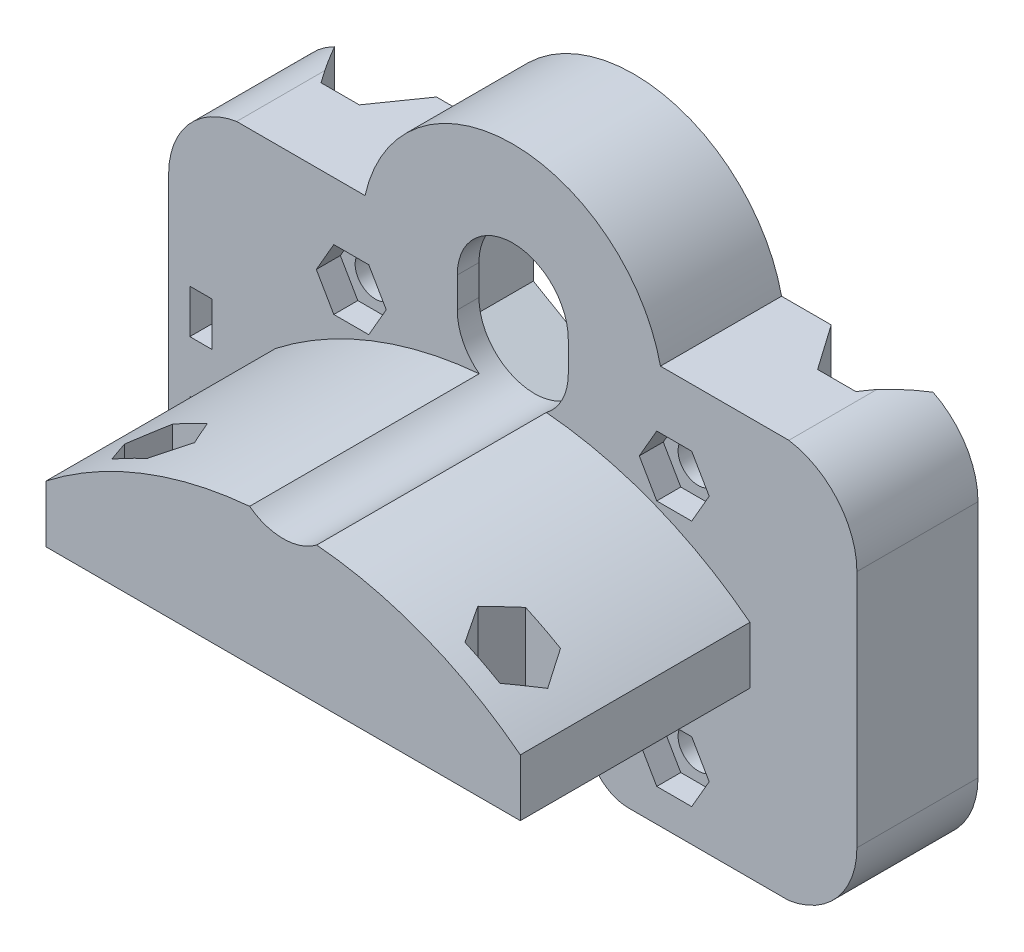
SolidWorks part; units mm, degrees
ref_plane "Front Plane" through (0, 0, 0) normal (0, 0, 1) x (1, 0, 0)
ref_plane "Top Plane" through (0, 0, 0) normal (0, 1, 0) x (1, 0, 0)
ref_plane "Right Plane" through (0, 0, 0) normal (1, 0, 0) x (0, 0, -1)
sketch "Sketch1" plane through (0, 0, 0) normal (0, 0, 1) x (1, 0, 0)
  line L0 (34.1, -14.8502) -> (34.1, 8.8502)
  line L1 (-34.1, -14.8502) -> (-34.1, 8.8502)
  line L2 (-14.6356, 16.75) -> (-27.3591, 16.75)
  line L3 (14.6356, 16.75) -> (27.3591, 16.75)
  line L4 (-11.5, -22.75) -> (-27.5591, -22.75)
  line L5 (11.5, -22.75) -> (27.3591, -22.75)
  line L6 (7.5, -18.75) -> (7.5, -16.0002)
  line L7 (-7.5, -16.0002) -> (-7.5, -18.75)
  line L8 (0, -8.5446) -> (0, 28.5) construction
  line L9 (34.1, 0) -> (-34.1, 0) construction
  arc A0 (27.3591, -22.75) -> (34.1, -14.8502) centre (26.1005, -14.8502) ccw
  arc A1 (7.5, -18.75) -> (11.5, -22.75) centre (11.5, -18.75) ccw
  arc A2 (34.1, 8.8502) -> (27.3591, 16.75) centre (26.1005, 8.8502) ccw
  arc A3 (-34.1, 8.8502) -> (-27.3591, 16.75) centre (-26.1005, 8.8502) cw
  arc A4 (-27.3591, -22.75) -> (-34.1, -14.8502) centre (-26.1005, -14.8502) cw
  arc A5 (-7.5, -18.75) -> (-11.5, -22.75) centre (-11.5, -18.75) cw
  arc A6 (14.6356, 16.75) -> (-14.6356, 16.75) centre (0, 13.5101) ccw
  arc A7 (7.5, -16.0892) -> (-7.5, -16.0892) centre (0, -16.0447) ccw
  circle A8 centre (16.0001, 8) radius 2
  circle A9 centre (16.0001, -16.5) radius 2
  circle A10 centre (-16.0001, -16.5) radius 2
  circle A11 centre (-16.0001, 8) radius 2
  dimension "D1" = 4
  dimension "D2" = 4.0001
  dimension "D3" = 7.9995
  dimension "D4" = 4.0001
  dimension "D5" = 7.5
  dimension "D6" = 14.9899
  dimension "D7" = 7.5001
  dimension "D8" = 14.6356
  dimension "D9" = 16.0001
  dimension "D10" = 26.1005
  dimension "D11" = 27.3591
  dimension "D12" = 8
  dimension "D13" = 8.8502
  dimension "D14" = 14.8502
  dimension "D15" = 16.0002
  dimension "D18" = 27.5591
  dimension "D25" = 16.5
extrude "Boss-Extrude1" add sketch "Sketch1" along normal blind 7.5 and the other way blind 4.5 contours A7 L6 A1 L5 A0 L0 A2 L3 A6 L2 A3 L1 A4 L4 A5 L7 A10 A9 A8 A11 region at (0, 0.408, 0)
sketch "Sketch3" plane through (0, 0, 7.5) normal (0, 0, 1) x (1, 0, 0)
  line L0 (0, 28.5) -> (0, -8.5446) construction
  line L1 (-19.4642, 8) -> (-17.7321, 5)
  line L2 (-17.7321, 5) -> (-14.268, 5)
  line L3 (-14.268, 5) -> (-12.536, 8)
  line L4 (-12.536, 8) -> (-14.268, 11)
  line L5 (-14.268, 11) -> (-17.7321, 11)
  line L6 (-5.5, 11.5) -> (-5.5, 14.5)
  line L7 (5.5, 11.5) -> (5.5, 14.5)
  line L8 (12.536, 8) -> (14.268, 11)
  line L9 (14.268, 5) -> (12.536, 8)
  line L10 (17.7321, 5) -> (14.268, 5)
  line L11 (19.4642, 8) -> (17.7321, 5)
  line L12 (17.7321, 11) -> (19.4642, 8)
  line L13 (14.268, 11) -> (17.7321, 11)
  line L14 (-34.1, -4.25) -> (34.1, -4.25) construction
  line L15 (-34.1, -14.8502) -> (-34.1, 8.8502) construction
  line L16 (-17.7321, -19.5) -> (-19.4642, -16.5)
  line L17 (-19.4642, -16.5) -> (-17.7321, -13.5)
  line L18 (-17.7321, -13.5) -> (-14.268, -13.5)
  line L19 (-14.268, -13.5) -> (-12.536, -16.5)
  line L20 (-12.536, -16.5) -> (-14.268, -19.5)
  line L21 (-14.268, -19.5) -> (-17.7321, -19.5)
  line L22 (17.7321, -19.5) -> (19.4642, -16.5)
  line L23 (19.4642, -16.5) -> (17.7321, -13.5)
  line L24 (17.7321, -13.5) -> (14.268, -13.5)
  line L25 (14.268, -13.5) -> (12.536, -16.5)
  line L26 (34.1, -14.8502) -> (34.1, 8.8502) construction
  line L27 (11.5, -22.75) -> (27.3591, -22.75) construction
  line L28 (-17.7321, 11) -> (-19.4642, 8)
  line L29 (12.536, -16.5) -> (14.268, -19.5)
  line L30 (14.268, -19.5) -> (17.7321, -19.5)
  arc A0 (14.6356, 16.75) -> (-14.6356, 16.75) centre (0, 13.5101) ccw construction
  circle A1 centre (-16.0001, 8) radius 3 construction
  arc A2 (7.5, -16.0892) -> (-7.5, -16.0892) centre (0, -16.0447) ccw construction
  arc A3 (-5.5, 14.5) -> (5.5, 14.5) centre (0, 14.5) cw
  arc A4 (-5.5, 11.5) -> (5.5, 11.5) centre (0, 11.5) ccw
  point P28 (0, 0)
  circle M1 centre (-16.0001, -16.5) radius 2
  circle M2 centre (16.0001, -16.5) radius 2
  circle M3 centre (16.0001, 8) radius 2
  circle M20 centre (-16.0001, 8) radius 2
  dimension "D1" = 6
  dimension "D2" = 12.25
  dimension "D3" = 5.5
  dimension "D5" = 5.5
  dimension "D4" = 14.5
  dimension "D6" = 3
  dimension "D7" = 5.5
sketch "Sketch4" plane through (0, 0, 7.5) normal (0, 0, 1) x (1, 0, 0)
  line L0 (5.5, 11.5) -> (5.5, 14.5) construction
  line L1 (-5.5, 11.5) -> (-5.5, 14.5) construction
  line L2 (5.5, 11.5) -> (5.5, 14.5)
  line L3 (-5.5, 11.5) -> (-5.5, 14.5)
  arc A0 (5.5, 14.5) -> (-5.5, 14.5) centre (0, 14.5) ccw construction
  arc A1 (-5.5, 11.5) -> (5.5, 11.5) centre (0, 11.5) ccw construction
  arc A2 (5.5, 14.5) -> (-5.5, 14.5) centre (0, 14.5) ccw
  arc A3 (-5.5, 11.5) -> (5.5, 11.5) centre (0, 11.5) ccw
extrude "Cut-Extrude2" cut sketch "Sketch4" against normal through all
extrude "Cut-Extrude3" cut sketch "Sketch3" against normal blind 2.38 contours L5 L28 L1 L2 L3 L4 M20 | L13 L8 L9 L10 L11 L12 M3 | L21 L20 L19 L18 L17 L16 M1 | L29 L30 L22 L23 L24 L25 M2 region at (-18.5188, 9.4542, 7.5) region at (13.4814, 9.4542, 7.5) region at (-18.5188, -17.9542, 7.5) region at (16.0001, -19.4084, 7.5)
sketch "Sketch6" plane through (0, 0, 7.5) normal (0, 0, 1) x (1, 0, 0)
  line L1 (23.5, -6.45) -> (-23.5, -6.45)
  line L2 (-23.5, -0.8) -> (23.5, -0.8)
  line L3 (-23.5, -0.8) -> (23.5, -0.8)
  line L4 (0, -8.5446) -> (0, -0.8) construction
  line L5 (-23.5, -0.8) -> (-23.5, -6.45)
  line L6 (-23.5, -6.45) -> (23.5, -6.45)
  line L7 (23.5, -0.8) -> (23.5, -6.45)
  arc A0 (3.324, 7.1181) -> (23.5, -0.8) centre (0, -31.0158) cw
  arc A2 (-5.5, 11.5) -> (5.5, 11.5) centre (0, 11.5) ccw construction
  arc A3 (-3.324, 7.1181) -> (3.324, 7.1181) centre (0, 11.5) ccw
  arc A4 (7.5, -16.0892) -> (-7.5, -16.0892) centre (0, -16.0447) ccw construction
  arc A6 (-23.5, -0.8) -> (-3.324, 7.1181) centre (0, -31.0158) cw
  point P4 (0, -6.45)
  arc M30 (5.5, 11.5) -> (-5.5, 11.5) centre (0, 11.5) cw
  dimension "D4" = 38.2785
  dimension "D1" = 47
  dimension "D2" = 0.8
  dimension "D3" = 5.65
extrude "Boss-Extrude2" add sketch "Sketch6" along normal blind 22.75 contours L4 L1 L7 L3 | L6 L4 L2 L5 | A6 L2 L3 A0 M30 region at (11.75, -3.625, 7.5) region at (-11.75, -3.625, 7.5) region at (0, 2.3597, 7.5)
sketch "Sketch9" plane through (0, 0, 0) normal (0, 1, 0) x (1, 0, 0)
  line L0 (-23.5, -30.25) -> (-3.324, -30.25) construction
  line L1 (-19.2321, -22) -> (-20.9641, -25)
  line L2 (-20.9641, -25) -> (-19.2321, -28)
  line L3 (-19.2321, -28) -> (-15.7679, -28)
  line L4 (-15.7679, -28) -> (-14.0359, -25)
  line L5 (-14.0359, -25) -> (-15.7679, -22)
  line L6 (-15.7679, -22) -> (-19.2321, -22)
  line L7 (14.6356, 4.5) -> (-14.6356, 4.5) construction
  line L8 (-14.6356, 4.5) -> (-27.3591, 4.5) construction
  line L9 (0, 4.5) -> (0, -30.25) construction
  line L10 (-3.324, -30.25) -> (3.324, -30.25) construction
  line L11 (22.7061, 0) -> (19.5551, 4.5)
  line L12 (19.5551, 4.5) -> (29.647, 4.5)
  line L13 (29.647, 4.5) -> (26.4961, 0)
  line L14 (26.4961, 0) -> (22.7061, 0)
  line L15 (20.9641, -25) -> (19.2321, -28)
  line L16 (19.2321, -22) -> (20.9641, -25)
  line L17 (15.7679, -22) -> (19.2321, -22)
  line L18 (-29.647, 4.5) -> (-26.4961, 0)
  line L19 (14.0359, -25) -> (15.7679, -22)
  line L20 (-26.4961, 0) -> (-22.7061, 0)
  line L21 (-22.7061, 0) -> (-19.5551, 4.5)
  line L22 (15.7679, -28) -> (14.0359, -25)
  line L23 (19.2321, -28) -> (15.7679, -28)
  line L24 (-19.5551, 4.5) -> (-29.647, 4.5)
  line L31 (-23.5, -30.25) -> (-23.5, -7.5) construction
  circle A0 centre (17.5, -25) radius 1.8
  circle A1 centre (-17.5, -25) radius 3 construction
  circle A2 centre (-17.5, -25) radius 1.8
  point P19 (0, 0)
  point P22 (0, 4.5)
  point P31 (17.5, -25)
  dimension "D4" = 6
  dimension "D5" = 125
  dimension "D7" = 3.6
  dimension "D1" = 4.453
  dimension "D2" = 6
  dimension "D3" = 5.25
  dimension "D6" = 125
  dimension "D8" = 3.79
  dimension "D9" = 19.5551
extrude "Cut-Extrude5" cut sketch "Sketch9" against normal through all both and the other way through all contours L13 | L21 L24 L18 L20 | L14 L13 L12 L11 | A0 | A2 region at (24.6011, 0, -2.5905) region at (-24.6011, 0, -2.5905)
extrude "Cut-Extrude6" cut sketch "Sketch9<7>" along normal blind 22.75 and the other way offset from surface 2.3496 contours L5 L6 L1 L2 L3 L4 A2 | L15 region at (-17.5, 0, 22.0917) region at (20.0187, 0, 26.4542) other way up to face at (-17.5, -6.45, 23.2)
sketch "Sketch9<7>" plane through (0, 0, 0) normal (0, 1, 0) x (1, 0, 0) same geometry as "Sketch9"
sketch "Sketch10" plane through (0, 0, 0) normal (1, 0, 0) x (0, 0, -1)
  circle A0 centre (-3.55, -1.87) radius 1.25
  circle A1 centre (-3.55, -11.33) radius 1.25
  point P0 (0, 0)
  dimension "D1" = 2.5
  dimension "D2" = 2.5
  dimension "D3" = 3.55
  dimension "D4" = 1.87
  dimension "D5" = 11.33
ref_plane "Plane1" through (-34.1, 0, 0) normal (-1, 0, 0) x (0, 0, 1)
sketch "Sketch11" plane through (-34.1, 0, 0) normal (-1, 0, 0) x (0, 0, 1)
  circle A0 centre (3.55, -1.87) radius 1.25 construction
  circle A1 centre (3.55, -11.33) radius 1.25 construction
  circle A2 centre (3.55, -1.87) radius 1.25
  circle A3 centre (3.55, -11.33) radius 1.25
extrude "Cut-Extrude8" cut sketch "Sketch11" against normal blind 6.1
sketch "Sketch12" plane through (0, 0, 0) normal (0, 0, 1) x (1, 0, 0)
  line L1 (-32, -4.0351) -> (-29.8, -4.0351)
  line L3 (-32, 0.2951) -> (-29.8, 0.2951)
  line L6 (-32, 0.2951) -> (-29.8, 0.2951)
  line L7 (-32, -4.0351) -> (-29.8, -4.0351)
  line L8 (-32, -9.1649) -> (-29.8, -9.1649)
  line L9 (-32, -13.4951) -> (-29.8, -13.4951)
  line L10 (-32, 0.2951) -> (-32, -4.0351)
  line L11 (-29.8, -4.0351) -> (-29.8, 0.2951)
  line L12 (-29.8, -9.1649) -> (-29.8, -13.4951)
  line L13 (-32, -9.1649) -> (-32, -13.4951)
ref_plane "Plane2" through (0, 0, 7.5) normal (0, 0, 1) x (1, 0, 0)
sketch "Sketch13" plane through (0, 0, 7.5) normal (0, 0, 1) x (1, 0, 0)
  line L0 (-32, 0.2951) -> (-29.8, 0.2951) construction
  line L1 (-32, 0.2951) -> (-29.8, 0.2951) construction
  line L2 (-29.8, -4.0351) -> (-29.8, 0.2951) construction
  line L3 (-32, 0.2951) -> (-32, -4.0351) construction
  line L4 (-32, -4.0351) -> (-29.8, -4.0351) construction
  line L5 (-32, -4.0351) -> (-29.8, -4.0351) construction
  line L6 (-32, -9.1649) -> (-29.8, -9.1649) construction
  line L7 (-29.8, -9.1649) -> (-29.8, -13.4951) construction
  line L8 (-32, -13.4951) -> (-29.8, -13.4951) construction
  line L9 (-32, -9.1649) -> (-32, -13.4951) construction
  line L10 (-32, 0.2951) -> (-29.8, 0.2951)
  line L11 (-32, 0.2951) -> (-29.8, 0.2951)
  line L12 (-29.8, -4.0351) -> (-29.8, 0.2951)
  line L13 (-32, 0.2951) -> (-32, -4.0351)
  line L14 (-32, -4.0351) -> (-29.8, -4.0351)
  line L15 (-32, -4.0351) -> (-29.8, -4.0351)
  line L16 (-32, -9.1649) -> (-29.8, -9.1649)
  line L17 (-29.8, -9.1649) -> (-29.8, -13.4951)
  line L18 (-32, -13.4951) -> (-29.8, -13.4951)
  line L19 (-32, -9.1649) -> (-32, -13.4951)
extrude "Cut-Extrude9" cut sketch "Sketch13" against normal blind 5.3 contours L13 L14 L12 L10 | L16 L19 L18 L17 region at (-30.9, -1.87, 7.5) region at (-30.9, -11.33, 7.5)
sketch "Sketch14" plane through (0, 0, 0) normal (0, 0, 1) x (1, 0, 0)
  line L4 (9.9593, 20.25) -> (0, 26)
  line L5 (-9.9593, 20.25) -> (0, 26)
  line L6 (-9.9593, 5.75) -> (0, 0)
  line L7 (0, 0) -> (9.9593, 5.75)
  line L8 (9.9593, 20.25) -> (9.9593, 5.75)
  line L9 (-9.9593, 20.25) -> (-9.9593, 5.75)
  point P8 (0, 0)
sketch "Sketch15" plane through (0, 0, -4.5) normal (0, 0, -1) x (-1, 0, 0)
  line L6 (0, 26) -> (-9.9593, 20.25)
  line L7 (9.9593, 20.25) -> (0, 26)
  line L8 (9.9593, 5.75) -> (9.9593, 20.25)
  line L9 (0, 0) -> (9.9593, 5.75)
  line L10 (-9.9593, 5.75) -> (0, 0)
  line L11 (-9.9593, 20.25) -> (-9.9593, 5.75)
  line L12 (0, 26) -> (-9.9593, 20.25)
  line L13 (9.9593, 20.25) -> (0, 26)
  line L14 (9.9593, 5.75) -> (9.9593, 20.25)
  line L15 (0, 0) -> (9.9593, 5.75)
  line L16 (-9.9593, 5.75) -> (0, 0)
  line L17 (-9.9593, 20.25) -> (-9.9593, 5.75)
  dimension "D1" = 0
extrude "Cut-Extrude10" cut sketch "Sketch15" against normal blind 9.85
